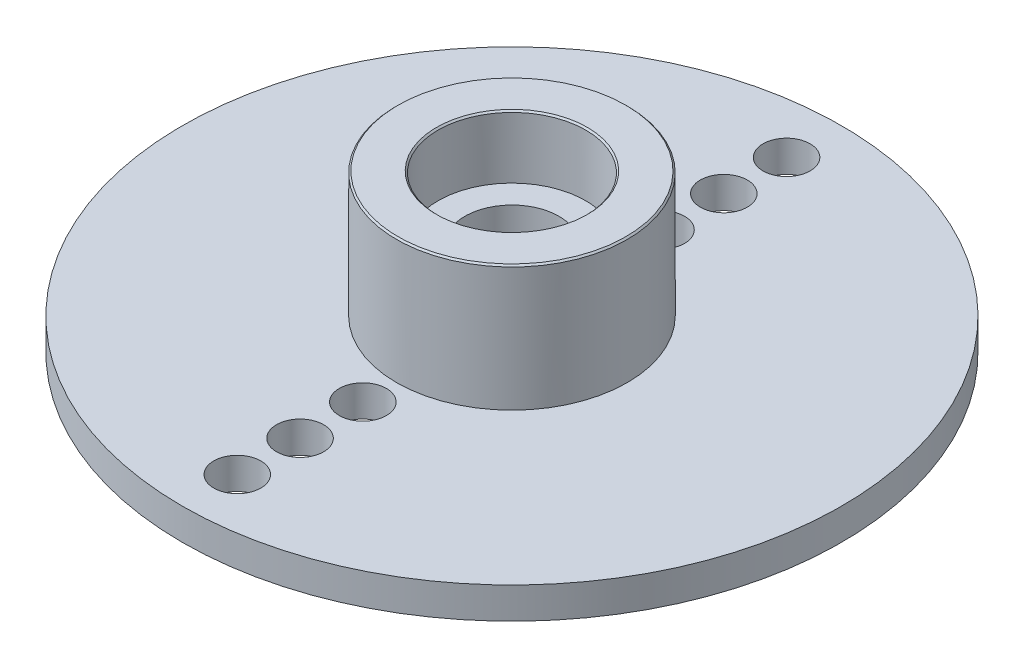
SolidWorks part; units mm, degrees
ref_plane "Ön Düzlem" through (0, 0, 0) normal (0, 0, 1) x (1, 0, 0)
ref_plane "Üst Düzlem" through (0, 0, 0) normal (0, 1, 0) x (1, 0, 0)
ref_plane "Sağ Düzlem" through (0, 0, 0) normal (1, 0, 0) x (0, 0, -1)
sketch "Sketch1" plane through (0, 0, 0) normal (0, 1, 0) x (1, 0, 0)
  line L0 (0, 10) -> (0, 3.6793) construction
  line L2 (-2.5, 0) -> (-2.5, -2.6995) construction
  line L5 (0, 0.75) -> (0, -2.9182) construction
  line L6 (0, -15.5) -> (0, -19.3684) construction
  line L7 (0, 0.75) -> (0, -10) construction
  line L9 (-3.6793, 0) -> (8.7348, 0) construction
  line L10 (0, 12) -> (0, 11.5) construction
  line L12 (0, -11.5) -> (0, -12) construction
  line L13 (0, -13.5) -> (0, -14.75) construction
  arc A0 (2.5, 14.75) -> (2.4912, 14.9596) centre (0, 14.75) ccw construction
  circle A7 centre (0, 0) radius 3.6793 construction
  circle A10 centre (0, 8.75) radius 0.75
  circle A11 centre (0, 6.75) radius 0.75
  circle A12 centre (0, 4.75) radius 0.75
  circle A13 centre (0, -4.75) radius 0.75
  circle A14 centre (0, -6.75) radius 0.75
  circle A15 centre (0, -8.75) radius 0.75
  circle A19 centre (0, 0) radius 0.75
  circle A20 centre (0, 0) radius 10.5
  arc A22 (-2.4912, 14.9596) -> (-2.5, 14.75) centre (0, 14.75) ccw construction
  point P2 (0, 0)
  point P25 (3.75, 0)
  point P28 (-3.75, 0)
  dimension "D1" = 2.5
  dimension "D7" = 1.5
  dimension "D8" = 21
  dimension "D3" = 3.75
extrude "Boss-Extrude2" add sketch "Sketch1" along normal blind 1 contours A19 A15 A13 A12 A11 A10 A14 region at (-10.203, 0, 0)
sketch "Sketch2" plane through (0, 0, 0) normal (0, -1, 0) x (1, 0, 0)
  circle A0 centre (0, 0) radius 1.5
  circle A1 centre (0, 0) radius 3.6793 construction
  circle A2 centre (0, 0) radius 3.6793
  dimension "D1" = 3
extrude "Boss-Extrude6" add sketch "Sketch2" against normal blind 5 contours A0 | A2
sketch "Sketch4" plane through (0, 0, 0) normal (0, -1, 0) x (1, 0, 0)
  circle A0 centre (0, 0) radius 0.75 construction
  circle A1 centre (0, 0) radius 0.75
extrude "Boss-Extrude7" add sketch "Sketch4" against normal up to surface (1 mm away) up to face at (0, 1, 0.75)
sketch "Sketch5" plane through (0, 0, 0) normal (0, -1, 0) x (1, 0, 0)
  circle A0 centre (0, 0) radius 1.5
  dimension "D1" = 3
extrude "Cut-Extrude2" cut sketch "Sketch5" against normal blind 0.5
extrude "Cut-Extrude3" cut sketch "Sketch1<5>" along normal through all contours A19
sketch "Sketch1<5>" plane through (0, 0, 0) normal (0, 1, 0) x (1, 0, 0) same geometry as "Sketch1"
sketch "Sketch6" plane through (0, 5, 0) normal (0, 1, 0) x (1, 0, 0)
  circle A0 centre (0, 0) radius 2.355
  dimension "D1" = 4.71
extrude "Cut-Extrude4" cut sketch "Sketch6" against normal blind 2
chamfer "Chamfer1" distance 0.05 angle 45 2 edges at (0, 5, -3.6793) (0, 5, 2.355)
